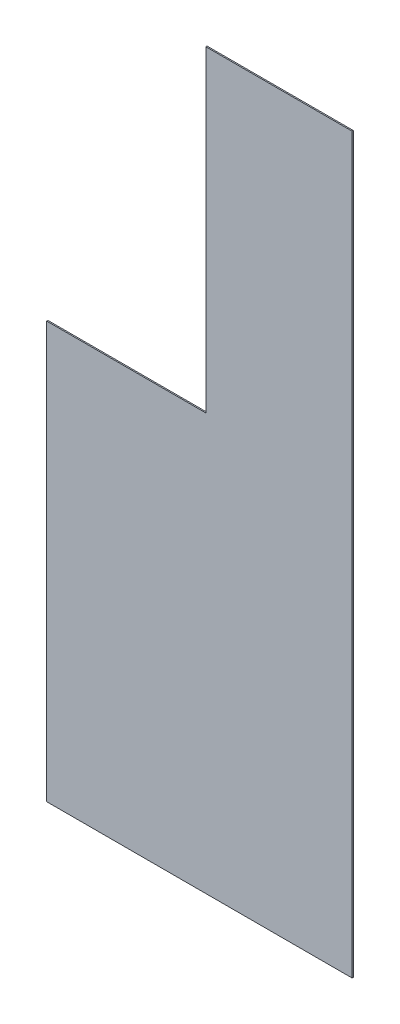
SolidWorks part; units mm, degrees
material "Hardox"
ref_plane "Ön Düzlem" through (0, 0, 0) normal (0, 0, 1) x (1, 0, 0)
ref_plane "Üst Düzlem" through (0, 0, 0) normal (0, 1, 0) x (1, 0, 0)
ref_plane "Sağ Düzlem" through (0, 0, 0) normal (1, 0, 0) x (0, 0, -1)
sketch "Çizim1" plane through (0, 0, 0) normal (0, 0, 1) x (1, 0, 0)
  line L0 (0, 0) -> (0, 3415)
  line L1 (0, 3415) -> (1305, 3415)
  line L2 (1305, 3415) -> (1305, 6017)
  line L3 (1305, 6017) -> (2505, 6017)
  line L4 (2505, 6017) -> (2505, 0)
  line L5 (2505, 0) -> (0, 0)
  dimension "D1" = 3415
  dimension "D2" = 1305
  dimension "D3" = 2602
  dimension "D4" = 1200
  dimension "D5" = 2505
  dimension "D6" = 6017
base flange "Taban-Flanş1" sketch "Çizim1" thickness 10 reverse thickness direction no parameters "D1"=4
sketch "Büküm-Çizgileri1" [suppressed] plane through (0, 0, 0) normal (0, 1, 0) x (1, 0, 0)
sketch "Sınırlandırma-Kutusu1" [suppressed] plane through (0, 0, 0) normal (0, 1, 0) x (1, 0, 0)
sheet metal parameters "Sac-Levha1" thickness 10 parameters "D1"=4
flat pattern "Düz-Çoğaltma1" [suppressed]
sketch "Büküm-Çizgileri2" plane through (0, 0, 0) normal (0, 1, 0) x (1, 0, 0)
sketch3d "Sınırlandırma-Kutusu2" [suppressed]
  line L0 (2505, 6017, 0) -> (2505, 0, 0) construction
  line L1 (0, 6017, 0) -> (0, 0, 0) construction
  line L2 (2505, 6017, 0) -> (0, 6017, 0) construction
  line L3 (2505, 0, 0) -> (0, 0, 0) construction
